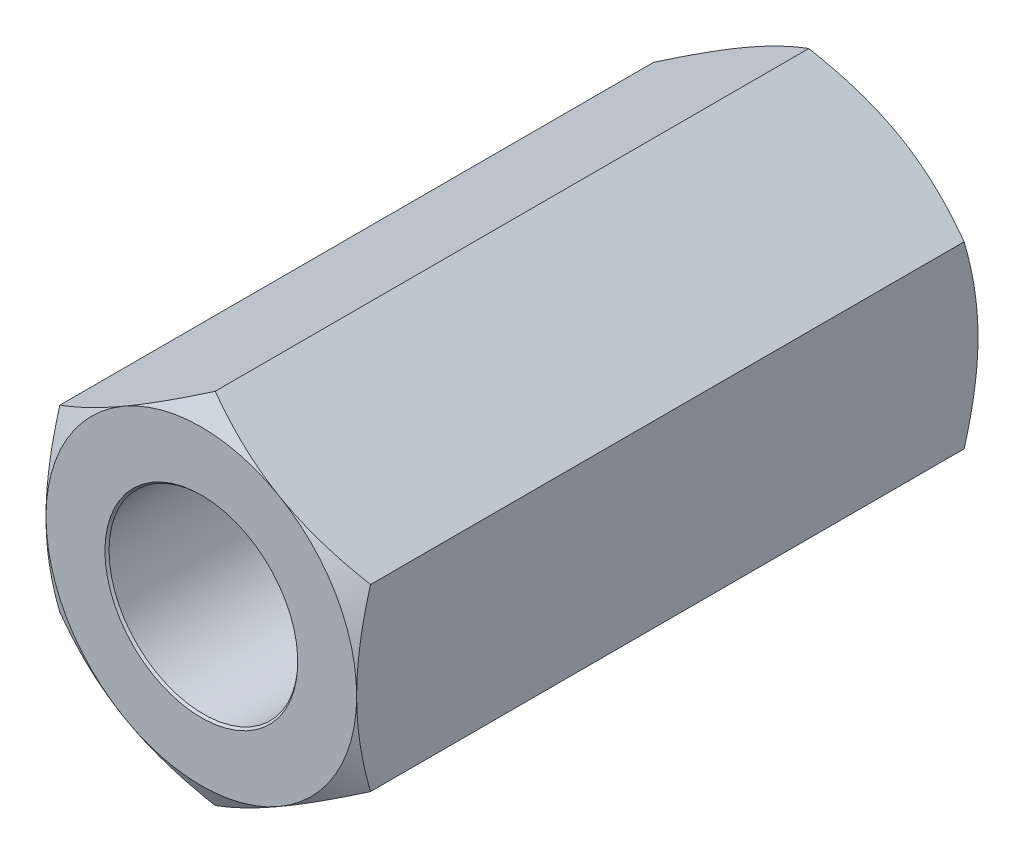
SolidWorks part; units mm, degrees
material "AISI 304"
ref_plane "Front Plane" through (0, 0, 0) normal (0, 0, 1) x (1, 0, 0)
ref_plane "Top Plane" through (0, 0, 0) normal (0, 1, 0) x (1, 0, 0)
ref_plane "Right Plane" through (0, 0, 0) normal (1, 0, 0) x (0, 0, -1)
sketch "Sketch3" plane through (0, 0, 0) normal (1, 0, 0) x (0, 0, -1)
  line L0 (-7.9375, 0) -> (7.9375, 0) construction
  line L1 (0, 3.9688) -> (0, -3.9688) construction
  line L2 (-7.9375, 2.413) -> (-7.9375, -2.413) construction
  point P2 (-4.7625, 0)
  point P3 (4.7625, 0)
  dimension "Length" = 15.875
  dimension "Min Thread Length" = 12.7
  dimension "D1" = 12.7
  dimension "Thread Dia" = 4.826
  dimension "Hex" = 7.9375
sketch "Sketch1" plane through (0, 0, 0) normal (0, 0, 1) x (1, 0, 0)
  line L1 (0, 4.5827) -> (-3.9688, 2.2914)
  line L2 (-3.9688, 2.2914) -> (-3.9688, -2.2914)
  line L3 (-3.9688, -2.2914) -> (0, -4.5827)
  line L4 (0, -4.5827) -> (3.9688, -2.2914)
  line L5 (3.9688, -2.2914) -> (3.9688, 2.2914)
  line L6 (3.9688, 2.2914) -> (0, 4.5827)
  circle A0 centre (0, 0) radius 3.9688 construction
  circle A1 centre (0, 0) radius 2.413
extrude "Extrude1" add sketch "Sketch1" along normal up to vertex (7.9375 mm away) and the other way up to vertex (7.9375 mm away) up to point (0, 0, 7.9375) other way up to point (0, 0, -7.9375)
sketch "Sketch11" plane through (0, 0, -7.9375) normal (0, 0, -1) x (-1, 0, 0)
  circle A0 centre (0, 0) radius 2.413 construction
  circle A1 centre (0, 0) radius 2.413
curve "Helix/Spiral1" pitch 0.7937 height 16.6687 turns 21 parameters "Pitch"=0.7937
sketch "Sketch12" plane through (0, 0, 0) normal (1, 0, 0) x (0, 0, -1)
  line L0 (8.632, 2.413) -> (7.9375, 2.413)
  line L1 (8.632, 2.413) -> (8.3344, 1.8974)
  line L2 (8.3344, 1.8974) -> (8.2352, 1.8974)
  line L3 (8.2352, 1.8974) -> (7.9375, 2.413)
  line L4 (8.2848, 1.8974) -> (8.2848, 2.413) construction
  line L5 (8.4832, 2.1552) -> (8.0863, 2.1552) construction
  dimension "D1" = 0.0992
  dimension "D2" = 0.3969
  dimension "D3" = 60
sweep "Sweep1" [suppressed] add profiles "Sketch12" path "Helix/Spiral1"
sketch "Sketch6" plane through (0, 0, -7.9375) normal (0, 0, -1) x (-1, 0, 0)
  line L6 (0, 4.5827) -> (-3.9688, 2.2914)
  line L7 (-3.9688, 2.2914) -> (-3.9688, -2.2914)
  line L8 (-3.9688, -2.2914) -> (0, -4.5827)
  line L9 (0, -4.5827) -> (3.9688, -2.2914)
  line L10 (3.9688, -2.2914) -> (3.9688, 2.2914)
  line L11 (3.9688, 2.2914) -> (0, 4.5827)
  line L12 (0, 4.5827) -> (-3.9688, 2.2914)
  line L13 (-3.9688, 2.2914) -> (-3.9688, -2.2914)
  line L14 (-3.9688, -2.2914) -> (0, -4.5827)
  line L15 (0, -4.5827) -> (3.9688, -2.2914)
  line L16 (3.9688, -2.2914) -> (3.9688, 2.2914)
  line L17 (3.9688, 2.2914) -> (0, 4.5827)
  dimension "D1" = 0
extrude "Extrude2" [suppressed] cut sketch "Sketch6" along normal through all
sketch "Sketch7" plane through (0, 0, -7.9375) normal (0, 0, -1) x (-1, 0, 0)
  circle A2 centre (0, 0) radius 2.4638
  circle A3 centre (0, 0) radius 2.4638
  dimension "D1" = 0.0508
extrude "Extrude3" cut sketch "Sketch7" against normal through all draft 43
sketch "Sketch8" plane through (0, 0, -7.9375) normal (0, 0, -1) x (-1, 0, 0)
  circle A0 centre (0, 0) radius 3.9688 construction
  circle A1 centre (0, 0) radius 3.9688
extrude "Extrude4" cut sketch "Sketch8" against normal through all draft 60 flip side to cut
mirror "Mirror1" about plane through (0, 0, 0) normal (0, 0, 1) of "Extrude2", "Extrude3", "Extrude4"
sketch "Sketch9" [suppressed] plane through (0, 0, 0) normal (1, 0, 0) x (0, 0, -1)
  line L1 (-12.7, 2.4638) -> (12.7, 2.4638)
  line L2 (-12.7, 2.4638) -> (-12.7, 0)
  line L3 (-12.7, 0) -> (12.7, 0)
  line L4 (12.7, 2.4638) -> (12.7, 0)
  line L7 (-25.4, 0) -> (25.4, 0) construction
revolve "Revolve" [suppressed] add sketch "Sketch9" angle 360 about L0
sketch "Sketch10" [suppressed] plane through (0, 0, 0) normal (1, 0, 0) x (0, 0, -1)
  line L0 (25.4, 2.413) -> (12.7, 2.413)
  line L1 (-25.4, 2.413) -> (-12.7, 2.413)
  line L2 (12.7, 2.413) -> (12.7, -2.413)
  line L3 (-25.4, -2.4638) -> (-12.7, -2.4638)
  line L4 (-12.7, 2.413) -> (-12.7, -2.4638)
  line L5 (12.7, -2.413) -> (25.4, -2.413)
equation "\"D1@Sketch3\" = \"Min Thread Length@Sketch3\""
equation "\"D3@Helix/Spiral1\" = \"Length@Sketch3\"+\"Pitch@Helix/Spiral1\""
equation "\"D1@Sketch12\" = \"Pitch@Helix/Spiral1\"*.125"
equation "\"D2@Sketch12\" = \"Pitch@Helix/Spiral1\"*.5"
